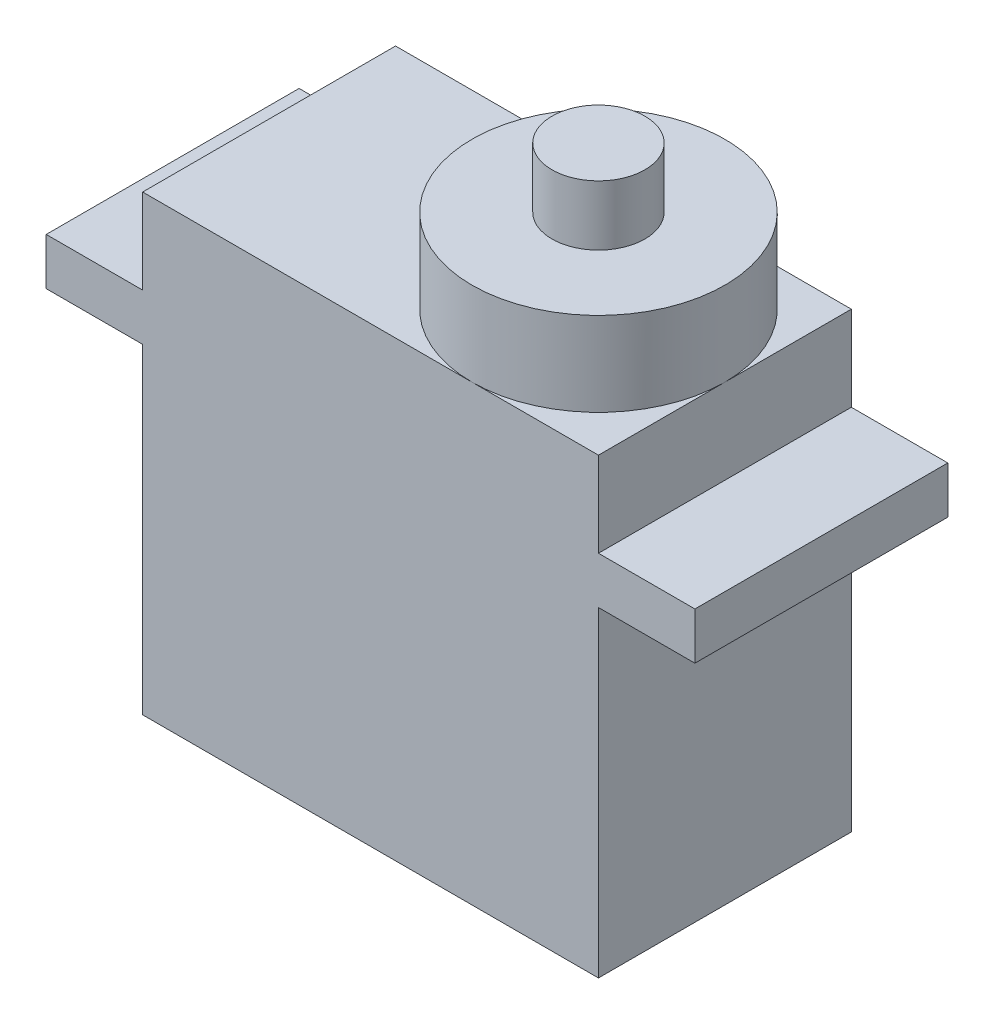
SolidWorks part; units mm, degrees
ref_plane "Front Plane" through (0, 0, 0) normal (0, 0, 1) x (1, 0, 0)
ref_plane "Top Plane" through (0, 0, 0) normal (0, 1, 0) x (1, 0, 0)
ref_plane "Right Plane" through (0, 0, 0) normal (1, 0, 0) x (0, 0, -1)
sketch "Sketch1" plane through (0, 0, 0) normal (0, 1, 0) x (1, 0, 0)
  line L0 (0, 0) -> (-19.1517, 0)
  line L1 (-11.4, -6.325) -> (11.4, -6.325)
  line L2 (-11.4, -6.325) -> (-11.4, 6.325)
  line L3 (-11.4, 6.325) -> (11.4, 6.325)
  line L4 (11.4, -6.325) -> (11.4, 6.325)
  line L5 (-16.225, -6.325) -> (16.225, -6.325)
  line L6 (-16.225, -6.325) -> (-16.225, 6.325)
  line L7 (-16.225, 6.325) -> (16.225, 6.325)
  line L8 (16.225, -6.325) -> (16.225, 6.325)
  line L9 (0, 0) -> (0, 17.5504)
  circle A0 centre (5.075, 0) radius 6.325
  circle A1 centre (5.075, 0) radius 2.325
  point P13 (0, 6.325)
  point P15 (-16.225, 0)
  point P16 (0, 6.325)
  dimension "D4" = 4.65
  dimension "D1" = 22.8
  dimension "D2" = 12.65
  dimension "D3" = 32.45
extrude "Boss-Extrude1" add sketch "Sketch1" against normal blind 16.05 contours A0 L9 L3 L2 L0 | A0 L0 L2 L1 | A0 L9 L0 A1 | L9 A0 L0 | A0 L7 L9 | A0 L4 L3 | A0 L5 L4 | A1 region at (0.1789, 0, -1.8875) region at (-0.5045, 0, -1.4363) region at (-5.5597, 0, 3.3689) region at (-5.9424, 0, -3.243) region at (1.212, 0, -5.5963) region at (9.9872, 0, 4.9122) region at (9.9872, 0, -4.9122) region at (5.075, 0, 0)
extrude "Boss-Extrude2" add sketch "Sketch1<3>" along normal blind 2.35 contours L6 L5 L2 L0 | A0 L0 L2 L1 | A0 L9 L3 L2 L0 | L7 L6 L0 L2 | A1 | A0 L9 L0 A1 | L9 A0 L0 | A0 L7 L9 | A0 L4 L3 | A0 L5 L4 | L5 L8 L7 L4 region at (0.1789, 0, -1.8875) region at (-0.5045, 0, -1.4363) region at (-5.5597, 0, 3.3689) region at (-5.9424, 0, -3.243) region at (1.212, 0, -5.5963) region at (-13.8125, 0, 3.1625) region at (-13.8125, 0, -3.1625) region at (9.9872, 0, 4.9122) region at (9.9872, 0, -4.9122) region at (13.8125, 0, 0) region at (5.075, 0, 0)
sketch "Sketch1<3>" plane through (0, 0, 0) normal (0, 1, 0) x (1, 0, 0) same geometry as "Sketch1"
extrude "Boss-Extrude3" add sketch "Sketch1<4>" along normal blind 6.6 contours A0 L9 L3 L2 L0 | A0 L0 L2 L1 | A0 L9 L0 A1 | A0 L7 L9 | A0 L4 L3 | A0 L5 L4 | L9 A0 L0 | A1 region at (0.1789, 0, -1.8875) region at (-0.5045, 0, -1.4363) region at (-5.5597, 0, 3.3689) region at (-5.9424, 0, -3.243) region at (1.212, 0, -5.5963) region at (9.9872, 0, 4.9122) region at (9.9872, 0, -4.9122) region at (5.075, 0, 0)
sketch "Sketch1<4>" plane through (0, 0, 0) normal (0, 1, 0) x (1, 0, 0) same geometry as "Sketch1"
extrude "Boss-Extrude4" add sketch "Sketch1<5>" along normal blind 10.8 contours A0 L9 L0 A1 | A1 | L9 A0 L0 region at (0.1789, 0, -1.8875) region at (-0.5045, 0, -1.4363) region at (5.075, 0, 0)
sketch "Sketch1<5>" plane through (0, 0, 0) normal (0, 1, 0) x (1, 0, 0) same geometry as "Sketch1"
extrude "Boss-Extrude5" add sketch "Sketch1<6>" along normal blind 13.8 contours A1 region at (5.075, 0, 0)
sketch "Sketch1<6>" plane through (0, 0, 0) normal (0, 1, 0) x (1, 0, 0) same geometry as "Sketch1"
